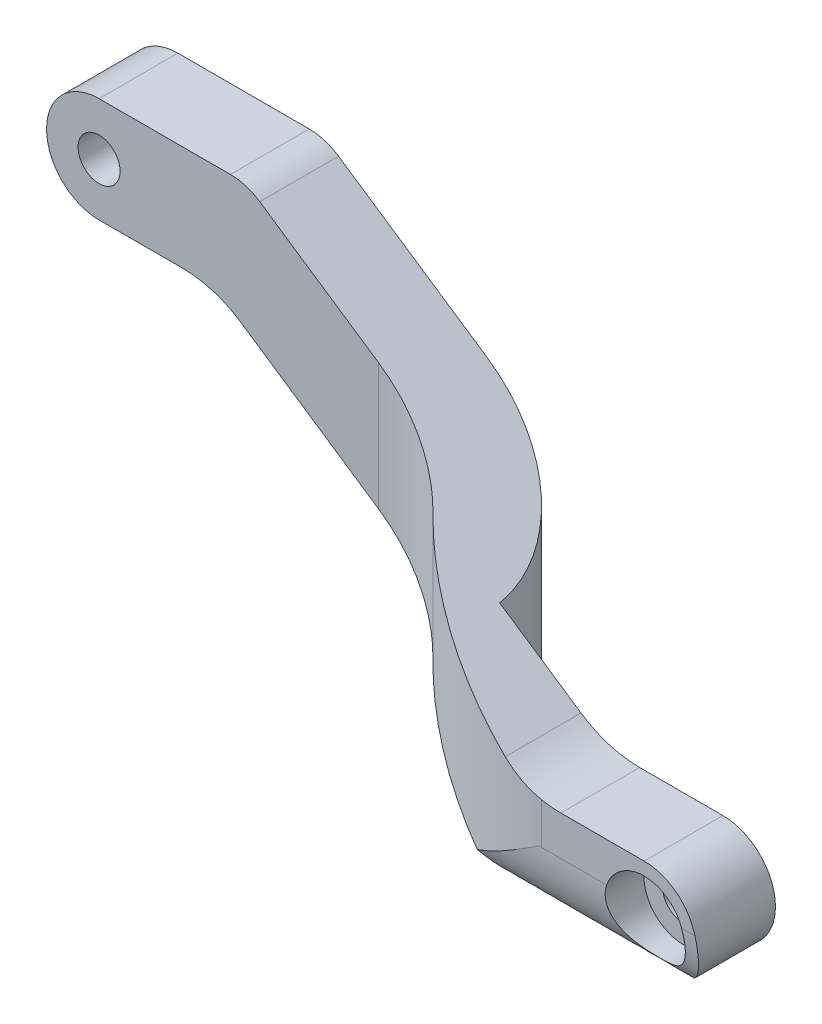
SolidWorks part; units mm, degrees
ref_plane "Front Plane" through (0, 0, 0) normal (0, 0, 1) x (1, 0, 0)
ref_plane "Top Plane" through (0, 0, 0) normal (0, 1, 0) x (1, 0, 0)
ref_plane "Right Plane" through (0, 0, 0) normal (1, 0, 0) x (0, 0, -1)
sketch "Sketch1" plane through (0, 0, 0) normal (0, 0, 1) x (1, 0, 0)
  line L0 (0, 0) -> (0, -5.5) construction
  line L1 (-25.25, 4.7631) -> (0, -5.5) construction
  line L2 (-25.25, 4.7631) -> (-28, 0) construction
  line L3 (-28, 0) -> (0, 0) construction
  line L4 (-28, 0) -> (-28, 8.6643) construction
  line L5 (-25.25, 4.7631) -> (-20.25, 4.7631) construction
  line L6 (-20.25, 4.7631) -> (-5, -5.5) construction
  line L7 (-5, -5.5) -> (0, -5.5) construction
  line L9 (-19.1333, 6.4224) -> (-4.3897, -3.5)
  line L10 (0, -7.5) -> (-5, -7.5)
  line L11 (0, -3.5) -> (-4.3897, -3.5)
  line L12 (-25.25, 6.7631) -> (-20.25, 6.7631)
  line L13 (-25.25, 2.7631) -> (-20.8603, 2.7631)
  line L15 (-20.8603, 2.7631) -> (-6.1167, -7.1592)
  circle A0 centre (0, 0) radius 1 construction
  circle A1 centre (-28, 0) radius 1 construction
  circle A2 centre (-25.25, 4.7631) radius 0.8
  circle A3 centre (0, -5.5) radius 0.8
  arc A4 (-25.031, 6.7511) -> (-25.25, 2.7631) centre (-25.25, 4.7631) ccw
  arc A10 (-25.031, 6.7511) -> (-25.469, 2.7752) centre (-25.25, 4.7631) ccw
  arc A15 (0, -7.5) -> (0.6301, -3.6019) centre (0, -5.5) ccw
  arc A16 (0, -7.5) -> (0, -3.5) centre (0, -5.5) ccw
  arc A17 (-6.1167, -7.1592) -> (-5, -7.5) centre (-5, -5.5) ccw
  arc A18 (-19.1333, 6.4224) -> (-20.25, 6.7631) centre (-20.25, 4.7631) ccw
  dimension "D1" = 28
  dimension "D2" = 2
  dimension "D5" = 2
  dimension "D6" = 4
  dimension "D7" = 5.5
  dimension "D9" = 5
  dimension "D3" = 30
  dimension "D4" = 5.5
  dimension "D8" = 5
extrude "Boss-Extrude1" add sketch "Sketch1" along normal blind 3 and the other way blind 4.5 contours A4 A2 | A4 | A3 region at (-12.625, -0.3684, 0)
fillet "Fillet1" radius 4 2 edges at (-4.3897, -3.5, -0.75) (-20.8603, 2.7631, -0.75)
sketch "Sketch4" plane through (0, 0, 0) normal (0, 1, 0) x (1, 0, 0)
  line L0 (-19.1333, 4.5) -> (-5.4023, 4.5) construction
  line L1 (-8.5, 4.5) -> (2, 4.5)
  line L2 (-8.5, 4.5) -> (-8.5, 0)
  line L3 (-8.5, 0) -> (2, 0)
  line L4 (2, 4.5) -> (2, 0)
  line L5 (2, -3) -> (2, 4.5) construction
  dimension "D1" = 4.5
  dimension "10.5" = 10.5
extrude "Cut-Extrude2" cut sketch "Sketch4" against normal through all both and the other way through all
sketch "Sketch5" plane through (0, 0, 0) normal (0, 1, 0) x (1, 0, 0)
  line L1 (-27.25, -3) -> (-12.25, -3)
  line L2 (-27.25, -3) -> (-27.25, 1.5)
  line L3 (-27.25, 1.5) -> (-12.25, 1.5)
  line L4 (-12.25, -3) -> (-12.25, 1.5)
  dimension "D1" = 15
  dimension "D2" = 4.5
extrude "Cut-Extrude3" cut sketch "Sketch5" against normal through all both and the other way through all
fillet "Fillet2" radius 10 1 edges at (-12.25, -0.6208, 3)
fillet "Fillet3" radius 5 1 edges at (-8.5, -3.1445, -4.5)
fillet "Fillet4" radius 5 1 edges at (-12.25, -0.6208, -1.5)
sketch "Sketch6" plane through (0, 0, 0) normal (1, 0, 0) x (0, 0, -1)
  line L1 (-4.5, -10) -> (-1.5, -10)
  line L2 (-4.5, -10) -> (-4.5, -5)
  line L3 (-4.5, -5) -> (-1.5, -5)
  line L4 (-1.5, -10) -> (-1.5, -5)
  line L5 (-4.5, -10) -> (-1.5, -5) construction
  line L6 (-4.5, -5) -> (-1.5, -10) construction
  ellipse E0 centre (-1.5, -4.9336) end of major axis (-1.5, -7.5) minor radius 1.5
  point P0 (-3, -7.5)
  dimension "D1" = 3
  dimension "D2" = 5
extrude "Cut-Extrude4" cut sketch "Sketch6" against normal through all both and the other way through all contours E0 L3 L2 L1 L4 region at (0, -7.849, 3.21)
sketch "Sketch7" plane through (0, 0, 3) normal (0, 0, 1) x (1, 0, 0)
  circle A0 centre (0, -5.5) radius 1.51
extrude "Cut-Extrude5" cut sketch "Sketch7" against normal blind 1.5
